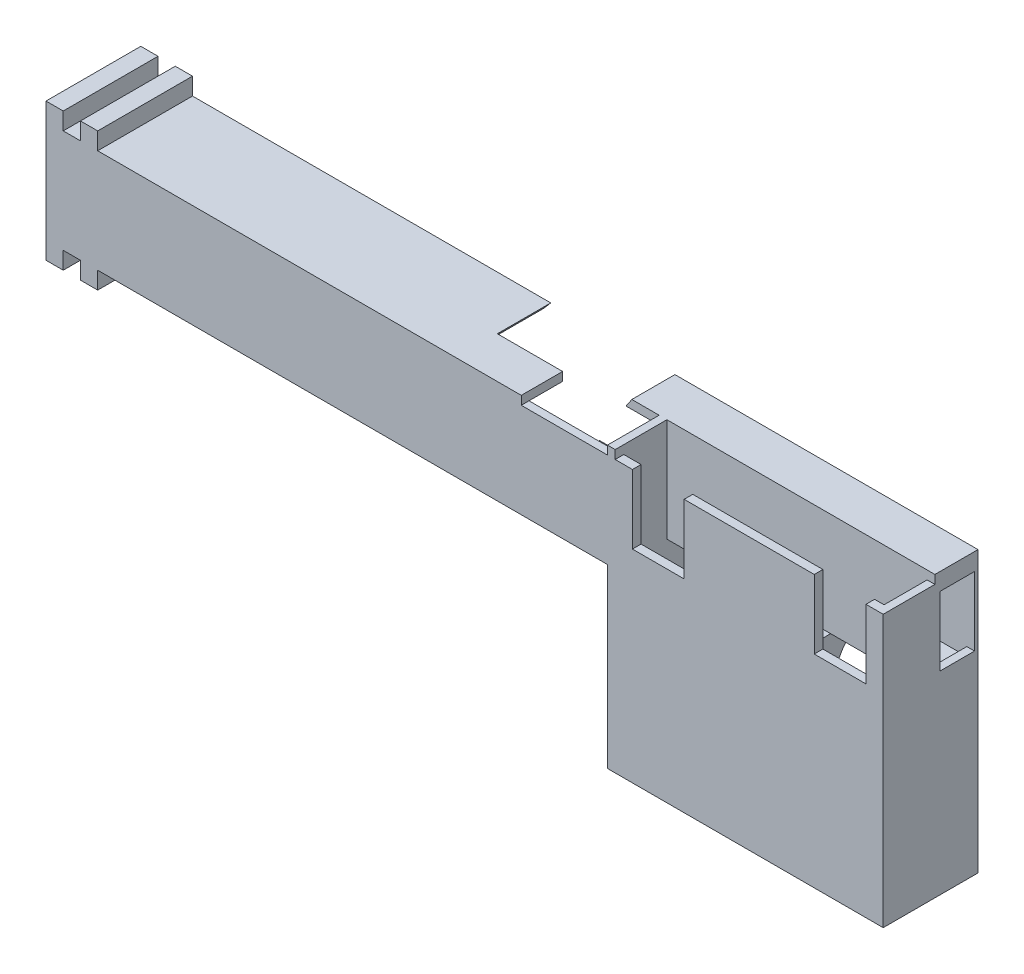
SolidWorks part; units mm, degrees
ref_plane "Front Plane" through (0, 0, 0) normal (0, 0, 1) x (1, 0, 0)
ref_plane "Top Plane" through (0, 0, 0) normal (0, 1, 0) x (1, 0, 0)
ref_plane "Right Plane" through (0, 0, 0) normal (1, 0, 0) x (0, 0, -1)
sketch "Sketch1" plane through (0, 0, 0) normal (0, 0, 1) x (1, 0, 0)
  line L3 (0, 20.5) -> (32, 20.5)
  line L4 (0.9, 20.5) -> (0.9, 31.5)
  line L5 (31.1, 20.5) -> (31.1, 31.5)
  line L6 (0.9, 31.5) -> (31.1, 31.5)
  line L7 (0.9, 20.5) -> (0.9, 6)
  line L8 (31.1, 20.5) -> (31.1, 6)
  line L9 (0.9, 6) -> (31.1, 6)
  line L10 (0, 20.5) -> (0, 0)
  line L11 (0, 0) -> (32, 0)
  line L12 (32, 0) -> (32, 20.5)
  line L13 (0, 20.5) -> (0, 31.5)
  line L14 (0, 31.5) -> (0.9, 31.5)
  line L15 (0, 31.5) -> (0.9, 31.5)
  line L16 (32, 20.5) -> (32, 31.5)
  line L17 (32, 31.5) -> (31.1, 31.5)
  line L21 (0, 31.5) -> (0.9, 31.5)
  line L22 (31.1, 31.5) -> (32, 31.5)
  line L31 (0, 31.5) -> (32, 31.5)
  line L41 (12.1, 20.5) -> (19.9, 20.5)
  line L42 (12.1, 20.5) -> (12.1, 6)
  line L43 (12.1, 6) -> (19.9, 6)
  line L44 (19.9, 20.5) -> (19.9, 6)
  point P0 (0, 0)
  point P11 (0, 20.5)
  point P32 (16, 6)
  point P40 (16, 20.5)
  dimension "D2" = 6
  dimension "D3" = 0.9
  dimension "D6" = 11
  dimension "D7" = 14.5
  dimension "D8" = 0.9
  dimension "D9" = 32
  dimension "D18" = 7.8
  dimension "D19" = 3.9
extrude "Boss-Extrude2" add sketch "Sketch1<3>" along normal blind 11 contours L11 L12 L3 L8 L9 L7 L10 | L14 L13 L3 L4 | L16 L17 L5 L3 | L4 L14 L13 region at (0.45, 26, 0) region at (16, 4.2266, 0) region at (31.55, 26, 0)
sketch "Sketch1<3>" plane through (0, 0, 0) normal (0, 0, 1) x (1, 0, 0) same geometry as "Sketch1"
extrude "Boss-Extrude3" add sketch "Sketch1<4>" along normal blind 5 contours L6 L4 L3 L5 region at (16, 26, 0)
sketch "Sketch1<4>" plane through (0, 0, 0) normal (0, 0, 1) x (1, 0, 0) same geometry as "Sketch1"
sketch "Sketch2" plane through (0, 6, 0) normal (0, 1, 0) x (1, 0, 0)
  line L0 (0.9, -11) -> (0.9, -10)
  line L1 (0.9, -11) -> (0.9, -5) construction
  line L2 (31.1, -11) -> (31.1, -10)
  line L3 (31.1, -11) -> (31.1, 0) construction
  line L4 (0.9, -10) -> (31.1, -10)
  line L5 (0.9, -11) -> (31.1, -11)
  dimension "D1" = 1
extrude "Boss-Extrude4" add sketch "Sketch2" along normal blind 25.5
extrude "Boss-Extrude5" add sketch "Sketch1" along normal blind 11 contours L44 L3 L42 L9 region at (16, 13.25, 0)
sketch "Sketch3" plane through (0, 0, 10) normal (0, 0, -1) x (-1, 0, 0)
  line L0 (-12.1, 6) -> (-12.1, 20.5) construction
  line L1 (-0.9, 6) -> (-12.1, 6)
  line L2 (-0.9, 6) -> (-0.9, 17)
  line L3 (-0.9, 17) -> (-12.1, 17)
  line L4 (-12.1, 6) -> (-12.1, 17)
  line L5 (-19.9, 6) -> (-19.9, 20.5) construction
  line L6 (-31.1, 6) -> (-19.9, 6)
  line L7 (-31.1, 6) -> (-31.1, 17)
  line L8 (-31.1, 17) -> (-19.9, 17)
  line L9 (-19.9, 6) -> (-19.9, 17)
  dimension "D1" = 11
  dimension "D2" = 11
extrude "Boss-Extrude6" add sketch "Sketch3" along normal blind 5
sketch "Sketch4" plane through (0, 31.5, 0) normal (0, 1, 0) x (1, 0, 0)
  line L0 (0, 0) -> (32, 0) construction
  line L1 (0, -0.4) -> (31.1, -0.4)
  line L2 (0, -0.4) -> (0, -4.4)
  line L3 (0, -4.4) -> (31.1, -4.4)
  line L4 (31.1, -0.4) -> (31.1, -4.4)
  line L6 (31.1, -10) -> (31.1, -5) construction
  line L8 (0, -11) -> (0, 0) construction
  dimension "D1" = 0.4
  dimension "D2" = 4
extrude "Cut-Extrude1" cut sketch "Sketch4" against normal blind 10
sketch "Sketch5" plane through (0, 31.5, 0) normal (0, 1, 0) x (1, 0, 0)
  line L0 (0, -11) -> (0, -4.4) construction
  line L1 (32, 0) -> (0, 0)
  line L2 (32, 0) -> (32, -5)
  line L3 (32, -5) -> (0, -5)
  line L4 (0, 0) -> (0, -5)
  line L5 (0.9, -5) -> (31.1, -5) construction
extrude "Boss-Extrude7" add sketch "Sketch5" along normal blind 1
sketch "Sketch7" plane through (0, 0, 0) normal (-1, 0, 0) x (0, 0, 1)
  line L0 (0, 32.5) -> (0, 0) construction
  line L1 (5, 32.5) -> (0, 32.5)
  line L2 (5, 32.5) -> (5, 31.5)
  line L3 (5, 31.5) -> (0, 31.5)
  line L4 (0, 32.5) -> (0, 31.5)
  line L5 (11, 31.5) -> (5, 31.5) construction
  line L6 (4.4, 21.5) -> (4.4, 31.5) construction
  line L7 (0, 21.5) -> (5, 21.5)
  line L8 (0, 21.5) -> (0, 20.4962)
  line L9 (0, 20.4962) -> (5, 20.4962)
  line L10 (5, 21.5) -> (5, 20.4962)
  line L11 (5, 31.5) -> (5, 21.5)
  line L12 (4.4, 31.5) -> (4.4, 21.5)
  line M5 (0.4, 31.5) -> (4.4, 31.5)
  line M7 (4.4, 21.5) -> (0.4, 21.5)
  line M10 (5, 31.5) -> (5, 32.5)
  line M11 (5, 32.5) -> (0, 32.5)
  line M12 (0, 32.5) -> (0, 0)
  dimension "D1" = 1.0038
  dimension "D2" = 5
extrude "Boss-Extrude8" add sketch "Sketch7" along normal blind 62.24 contours L10 L7 L9 M7 M12 | L3 M10 M11 M12 M5 region at (0, 32, 2.5) region at (0, 20.9981, 2.5)
sketch "Sketch8" plane through (0, 0, 5) normal (0, 0, 1) x (1, 0, 0)
  line L0 (-62.24, 32.5) -> (32, 32.5) construction
  line L1 (0.9, 31.5) -> (0, 31.5)
  line L2 (0.9, 31.5) -> (0.9, 32.5)
  line L3 (0.9, 32.5) -> (0, 32.5)
  line L4 (0, 31.5) -> (0, 32.5)
  line L5 (0, 31.5) -> (0, 0) construction
extrude "Boss-Extrude9" add sketch "Sketch8" along normal blind 6
sketch "Sketch9" plane through (0, 0, 0) normal (-1, 0, 0) x (0, 0, 1)
  line L0 (11, 32.5) -> (11, 0) construction
  line L3 (11, 31.5) -> (5, 31.5)
  line L5 (5, 20.4962) -> (11, 20.4962)
  line L6 (5, 20.4962) -> (5, 21.4995)
  line L7 (5, 21.4995) -> (11, 21.4995)
  line L8 (11, 20.4962) -> (11, 21.4995)
  line L10 (11, 31.5) -> (10.1, 31.5)
  line L11 (11, 31.5) -> (11, 21.4995)
  line L12 (11, 21.4995) -> (10.1, 21.4995)
  line L13 (10.1, 31.5) -> (10.1, 21.4995)
  line M1 (11, 0) -> (11, 32.5)
  line M7 (5, 21.5) -> (5, 20.4962)
  dimension "D1" = 1.0033
  dimension "D2" = 0.9
extrude "Boss-Extrude10" add sketch "Sketch9" along normal blind 62.26 contours L7 L5 M7 M1 | L3 L13 L7 M1 region at (0, 26.4998, 10.55) region at (0, 20.9978, 8)
sketch "Sketch10" plane through (0, 0, 5) normal (0, 0, 1) x (1, 0, 0)
  line L0 (-62.24, 32.5) -> (0, 32.5) construction
  line L1 (-10, 32.5) -> (-62.24, 32.5)
  line L2 (-10, 32.5) -> (-10, 31.5)
  line L3 (-10, 31.5) -> (-62.24, 31.5)
  line L4 (-62.24, 32.5) -> (-62.24, 31.5)
  dimension "D1" = 10
extrude "Boss-Extrude11" add sketch "Sketch10" along normal blind 6
sketch "Sketch11" plane through (0, 0, 0) normal (0, 0, -1) x (-1, 0, 0)
  circle A0 centre (71.2419, 77.6773) radius 81.7
  circle A1 centre (71.2419, 77.6773) radius 70.15
  point P0 (71.2419, 77.6773)
  dimension "D3" = 163.4
  dimension "D4" = 140.3
  dimension "D1" = 129.2
  dimension "D2" = 105.4
extrude "Cut-Extrude2" cut sketch "Sketch11" against normal blind 6.2
sketch "Sketch12" plane through (-62.24, 0, 0) normal (-1, 0, 0) x (0, 0, 1)
  line L0 (11, 31.5) -> (11, 21.5)
  line L1 (0, 21.5) -> (11, 21.5)
  line L2 (0, 21.5) -> (0, 20.4962)
  line L3 (0, 20.4962) -> (11, 20.4962)
  line L4 (11, 21.5) -> (11, 20.4962)
  line L5 (0, 32.5) -> (11, 32.5)
  line L6 (0, 32.5) -> (0, 31.5)
  line L7 (0, 31.5) -> (11, 31.5)
  line L8 (11, 32.5) -> (11, 31.5)
  line L9 (10.1, 31.5) -> (11, 31.5)
  line L10 (10.1, 31.5) -> (10.1, 21.5)
  line L11 (10.1, 21.5) -> (11, 21.5)
  line L12 (11, 31.5) -> (11, 21.5)
  line L14 (11, 20.4962) -> (11, 31.5) construction
  line M5 (5, 21.4995) -> (5, 21.5)
  line M6 (5, 21.5) -> (0, 21.5)
  line M7 (0, 21.5) -> (0, 20.4962)
  line M8 (0, 20.4962) -> (5, 20.4962)
  line M9 (5, 20.4962) -> (5, 21.4995)
  dimension "D1" = 11
  dimension "D2" = 1.0038
  dimension "D3" = 1
  dimension "D4" = 0.9
extrude "Boss-Extrude12" add sketch "Sketch12" along normal blind 2.91 contours L8 L5 L6 L7 | L7 L10 L1 L0 | L4 L1 L3 M5 M9 | M9 M5 M6 M7 M8 region at (-62.24, 26.5, 10.55) region at (-62.24, 32, 5.5) region at (-62.24, 20.9981, 8) region at (-62.24, 20.9981, 2.5)
sketch "Sketch14" plane through (0, 20.4962, 0) normal (0, -1, 0) x (-1, 0, 0)
  line L0 (65.15, 0) -> (30.6051, 0) construction
  line L1 (65.15, -11) -> (63.15, -11)
  line L2 (65.15, -11) -> (65.15, 0)
  line L3 (65.15, 0) -> (63.15, 0)
  line L4 (63.15, -11) -> (63.15, 0)
  line L5 (65.15, -11) -> (0, -11) construction
  line L6 (59.15, 0) -> (61.15, 0)
  line L7 (59.15, 0) -> (59.15, -11)
  line L8 (59.15, -11) -> (61.15, -11)
  line L9 (61.15, 0) -> (61.15, -11)
  dimension "D1" = 2
  dimension "D2" = 2
  dimension "D3" = 2
extrude "Boss-Extrude13" add sketch "Sketch14" along normal blind 2
sketch "Sketch15" plane through (0, 32.5, 0) normal (0, 1, 0) x (1, 0, 0)
  line L0 (-10, -11) -> (-65.15, -11) construction
  line L1 (-65.15, 0) -> (-63.15, 0)
  line L2 (-65.15, 0) -> (-65.15, -11)
  line L3 (-65.15, -11) -> (-63.15, -11)
  line L4 (-63.15, 0) -> (-63.15, -11)
  line L5 (-61.15, 0) -> (-59.15, 0)
  line L6 (-61.15, 0) -> (-61.15, -11)
  line L7 (-61.15, -11) -> (-59.15, -11)
  line L8 (-59.15, 0) -> (-59.15, -11)
  dimension "D1" = 2
extrude "Boss-Extrude14" add sketch "Sketch15" along normal blind 2
sketch "Sketch20" plane through (19.9, 0, 0) normal (1, 0, 0) x (0, 0, -1)
  line L0 (0, 20.5) -> (0, 6) construction
  line L1 (-5, 6) -> (-5, 17) construction
  ellipse E0 centre (0, 13.25) end of major axis (0, 6) minor radius 5
  dimension "D1" = 7.25
  dimension "D2" = 10
extrude "Cut-Extrude3" cut sketch "Sketch20" against normal blind 10
sketch "Sketch21" plane through (0, 0, 11) normal (0, 0, 1) x (1, 0, 0)
  line L0 (32, 31.5) -> (0.9, 31.5) construction
  line L1 (2.9, 31.5) -> (8.9, 31.5)
  line L2 (2.9, 31.5) -> (2.9, 23.5)
  line L3 (2.9, 23.5) -> (8.9, 23.5)
  line L4 (8.9, 31.5) -> (8.9, 23.5)
  line L6 (24, 31.5) -> (30, 31.5)
  line L7 (24, 31.5) -> (24, 23.5)
  line L8 (24, 23.5) -> (30, 23.5)
  line L9 (30, 31.5) -> (30, 23.5)
  dimension "D1" = 2
  dimension "D2" = 2
  dimension "D3" = 6
  dimension "D4" = 6
  dimension "D5" = 8
  dimension "D6" = 8
extrude "Cut-Extrude4" cut sketch "Sketch21" against normal blind 1
sketch "Sketch22" plane through (32, 0, 0) normal (1, 0, 0) x (0, 0, -1)
  line L0 (0, 0) -> (0, 32.5) construction
  line L1 (-4.4, 30.5) -> (-0.4, 30.5)
  line L2 (-4.4, 30.5) -> (-4.4, 22.5)
  line L3 (-4.4, 22.5) -> (-0.4, 22.5)
  line L4 (-0.4, 30.5) -> (-0.4, 22.5)
  line L5 (-4.4, 30.5) -> (-0.4, 22.5) construction
  line L6 (-4.4, 22.5) -> (-0.4, 30.5) construction
  line L8 (-5, 32.5) -> (0, 32.5) construction
  point P0 (-2.4, 26.5)
  dimension "D1" = 0.4
  dimension "D2" = 4
  dimension "D3" = 8
  dimension "D4" = 2
extrude "Cut-Extrude5" cut sketch "Sketch22" against normal blind 1
